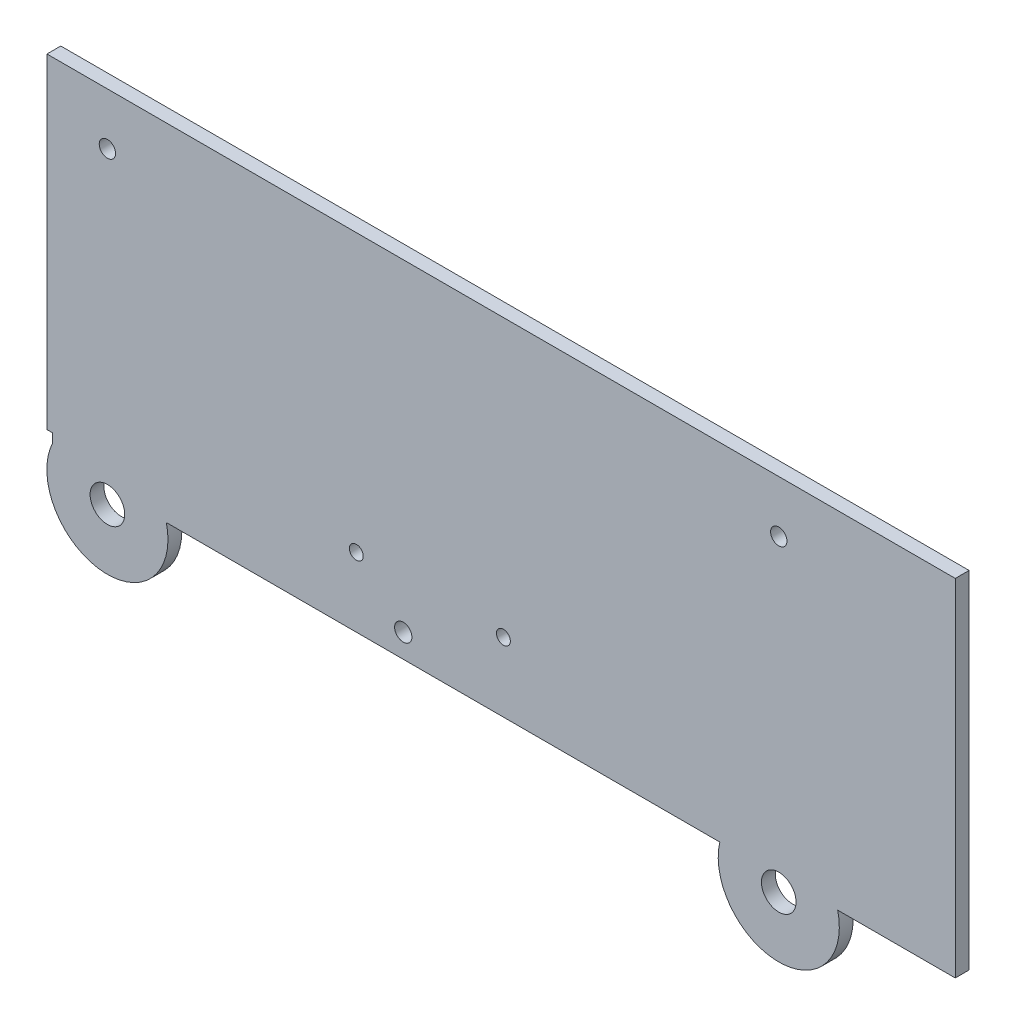
SolidWorks part; units mm, degrees
ref_plane "Front Plane" through (0, 0, 0) normal (0, 0, 1) x (1, 0, 0)
ref_plane "Top Plane" through (0, 0, 0) normal (0, 1, 0) x (1, 0, 0)
ref_plane "Right Plane" through (0, 0, 0) normal (1, 0, 0) x (0, 0, -1)
sketch "Sketch2" plane through (0, 0, 0) normal (0, 0, 1) x (1, 0, 0)
  line L1 (-143.383, -31.75) -> (143.383, -31.75)
  line L2 (-143.383, -31.75) -> (-143.383, 31.75)
  line L3 (-143.383, 31.75) -> (143.383, 31.75)
  line L4 (143.383, -31.75) -> (143.383, 31.75)
  line L5 (-143.383, -31.75) -> (143.383, 31.75) construction
  line L6 (-143.383, 31.75) -> (143.383, -31.75) construction
  line L16 (-143.383, 31.75) -> (143.383, 31.75)
  line L17 (-143.383, 31.75) -> (-143.383, 95.25)
  line L18 (-143.383, 95.25) -> (143.383, 95.25)
  line L19 (143.383, 31.75) -> (143.383, 95.25)
  circle A0 centre (-123.317, -36.83) radius 6.35
  circle A1 centre (123.063, -36.83) radius 6.35
  point P0 (0, 0)
  point P11 (0, 0)
  dimension "D3" = 20.066
  dimension "D5" = 5.08
  dimension "D7" = 63.5
  dimension "D1" = 63.5
  dimension "D2" = 286.766
  dimension "D6" = 20.32
extrude "Boss-Extrude1" add sketch "Sketch2" against normal blind 5.0749 contours A1 L1 L4 L3 L2 A0 | L3 L19 L18 L17 region at (0.0001, 0.0226, 0) region at (0, 63.5, 0)
ref_plane "Plane1" through (-143.383, 95.25, 0) normal (0, 1, 0) x (1, 0, 0)
ref_plane "Plane2" through (0, 0, -5.0749) normal (0, 0, -1) x (-1, 0, 0)
sketch "Sketch5" plane through (0, 0, -5.0749) normal (0, 0, -1) x (-1, 0, 0)
  line L5 (-143.383, -31.75) -> (-187.833, -31.75)
  line L6 (-143.383, -31.75) -> (-143.383, 95.25)
  line L7 (-143.383, 95.25) -> (-187.833, 95.25)
  line L8 (-187.833, -31.75) -> (-187.833, 95.25)
  dimension "D1" = 44.45
  dimension "D2" = 127
extrude "Boss-Extrude2" add sketch "Sketch5" against normal blind 5.0749
sketch "Sketch6" plane through (0, 0, -5.0749) normal (0, 0, -1) x (-1, 0, 0)
  line L0 (-116.713, -36.83) -> (-129.413, -36.83) construction
  line L1 (-123.063, -30.48) -> (-123.063, -43.18) construction
  line L3 (123.317, -30.48) -> (123.317, -43.18) construction
  line L4 (123.317, -43.18) -> (116.967, -36.83) construction
  line L6 (116.967, -36.83) -> (129.667, -36.83) construction
  circle A2 centre (-123.063, -36.83) radius 6.35 construction
  circle A3 centre (-123.063, -36.83) radius 22.225
  circle A4 centre (123.317, -36.83) radius 6.35 construction
  circle A5 centre (123.317, -36.83) radius 22.225
  dimension "D1" = 44.45
  dimension "D2" = 44.45
extrude "Boss-Extrude3" add sketch "Sketch6" against normal blind 5.0749
extrude "Cut-Extrude2" cut sketch "Sketch2<3>" against normal blind 5.588 contours A0 | A1
sketch "Sketch2<3>" plane through (0, 0, 0) normal (0, 0, 1) x (1, 0, 0) same geometry as "Sketch2"
sketch "Sketch8" plane through (0, 0, -5.0749) normal (0, 0, -1) x (-1, 0, 0)
  line L0 (145.5039, -24.13) -> (145.5039, 95.25) construction
  line L1 (198.383, 95.25) -> (88.383, 95.25) construction
  line L2 (143.383, -27.2746) -> (143.383, 95.25) construction
  line L4 (145.5039, 95.25) -> (142.7757, 95.25)
  line L5 (145.5039, 95.25) -> (145.5039, -24.13)
  line L6 (145.5039, -24.13) -> (142.7757, -24.13)
  line L7 (142.7757, 95.25) -> (142.7757, -24.13)
  dimension "D1" = 2.1209
extrude "Boss-Extrude4" add sketch "Sketch8" against normal blind 5.0749
sketch "Sketch9" plane through (0, 0, -5.0749) normal (0, 0, -1) x (-1, 0, 0)
  line L0 (-123.063, -43.18) -> (-123.063, 95.25) construction
  line L1 (145.5039, 95.25) -> (-187.833, 95.25) construction
  line L2 (-123.063, 95.25) -> (123.317, -43.18) construction
  line L3 (123.317, -43.18) -> (123.317, 95.25) construction
  line L4 (123.317, 95.25) -> (-123.063, -43.18) construction
  line L5 (-123.063, -43.18) -> (-123.063, 95.25) construction
  line L6 (-123.063, 95.25) -> (-123.063, 76.2) construction
  line L7 (-123.063, 76.2) -> (123.317, 76.2) construction
  circle A0 centre (-123.063, -36.83) radius 6.35 construction
  circle A1 centre (123.317, -36.83) radius 6.35 construction
  circle A2 centre (-123.063, 76.2) radius 3
  circle A3 centre (123.317, 76.2) radius 3
  dimension "D1" = 19.05
extrude "Cut-Extrude3" cut sketch "Sketch9" against normal blind 400.05
sketch "Sketch10" plane through (0, 0, -5.0749) normal (0, 0, -1) x (-1, 0, 0)
  line L0 (145.5039, -12.1559) -> (31.9659, -12.1559) construction
  line L1 (145.5039, -24.13) -> (145.5039, 95.25) construction
  line L2 (31.9659, -12.1559) -> (-22.0091, -12.1559) construction
  line L3 (-22.0091, -31.75) -> (-22.0091, -6.35)
  line L4 (101.6804, -31.75) -> (-101.4264, -31.75) construction
  line L5 (31.9659, -31.75) -> (31.9659, -6.35) construction
  line L6 (-11.6609, -31.75) -> (-11.6609, -23.114) construction
  line L7 (-22.0091, -23.114) -> (31.9659, -23.114)
  circle A0 centre (-22.0091, -6.35) radius 2.54
  circle A1 centre (31.9659, -6.35) radius 2.54
  circle A2 centre (14.7458, -23.114) radius 3.175
  dimension "D1" = 113.538
  dimension "D2" = 53.975
  dimension "D3" = 25.4
  dimension "D4" = 25.4
  dimension "D5" = 8.636
extrude "Cut-Extrude4" cut sketch "Sketch10" against normal blind 6.35 contours A0 | A1 | A2 region at (23.7544, -4.6047, -5.0749) region at (-31.9659, -6.35, -5.0749)
